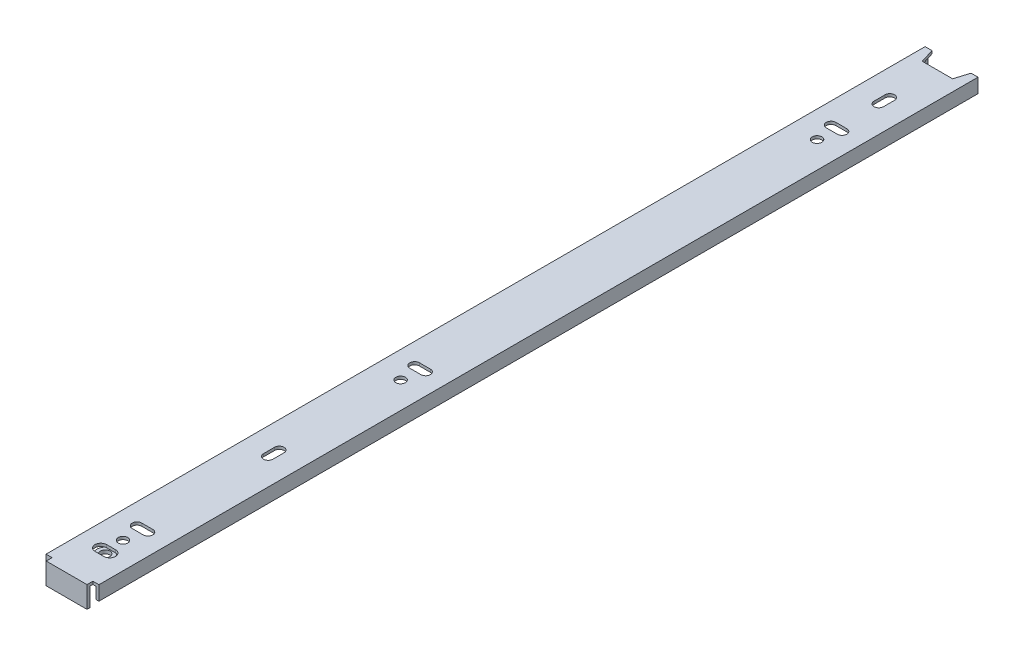
SolidWorks part; units mm, degrees
ref_plane "Front Plane" through (0, 0, 0) normal (0, 0, 1) x (1, 0, 0)
ref_plane "Top Plane" through (0, 0, 0) normal (0, 1, 0) x (1, 0, 0)
ref_plane "Right Plane" through (0, 0, 0) normal (1, 0, 0) x (0, 0, -1)
ref_plane "Plane1" through (0, -0.6, 0) normal (0, -1, 0) x (1, 0, 0)
sketch "Sketch1" plane through (0, -0.6, 0) normal (0, -1, 0) x (1, 0, 0)
  line L0 (3.75, 390.2) -> (3.1403, 397.9471)
  line L1 (-3.1403, 397.9471) -> (-3.75, 390.2)
  arc A0 (3.1403, 397.9471) -> (-3.1403, 397.9471) centre (0, 397.7) ccw
  arc A1 (-3.75, 390.2) -> (3.75, 390.2) centre (0, 390.2) ccw
extrude "Boss-Extrude1" add sketch "Sketch1" against normal blind 2.6
ref_plane "Plane2" through (0, 2, 0) normal (0, -1, 0) x (1, 0, 0)
sketch "Sketch2" plane through (0, 2, 0) normal (0, -1, 0) x (1, 0, 0)
  line L0 (-12.2, 408) -> (-12.2, 0)
  line L1 (-12.2, 0) -> (12.2, 0)
  line L2 (12.2, 0) -> (12.2, 408)
  line L3 (12.2, 408) -> (-12.2, 408)
  line L4 (-2.05, 392.9) -> (2.05, 392.9)
  line L5 (2.05, 387.5) -> (-2.05, 387.5)
  arc A0 (-2.05, 387.5) -> (-2.05, 392.9) centre (-2.05, 390.2) cw
  arc A1 (2.05, 392.9) -> (2.05, 387.5) centre (2.05, 390.2) cw
extrude "Boss-Extrude2" add sketch "Sketch2" against normal blind 1.3
sketch "Sketch3" plane through (0, 3.3, 0) normal (0, 1, 0) x (-1, 0, 0)
  line L0 (-12.2, 405.3) -> (-9.4, 405.3)
  line L1 (-9.4, 405.3) -> (-9.4, 408)
  line L2 (-9.4, 408) -> (-12.2, 408)
  line L3 (-12.2, 408) -> (-12.2, 405.3)
extrude "Cut-Extrude1" cut sketch "Sketch3" against normal through all
sketch "Sketch4" plane through (0, 2, 0) normal (0, -1, 0) x (1, 0, 0)
  line L0 (12.2, 0) -> (10.9, 0)
  line L1 (10.9, 0) -> (10.9, 405.3)
  line L2 (10.9, 405.3) -> (12.2, 405.3)
  line L3 (12.2, 405.3) -> (12.2, 0)
extrude "Boss-Extrude3" add sketch "Sketch4" along normal blind 5.3
sketch "Sketch5" plane through (0, 3.3, 0) normal (0, 1, 0) x (-1, 0, 0)
  line L0 (9.4, 405.3) -> (12.2, 405.3)
  line L1 (12.2, 405.3) -> (12.2, 408)
  line L2 (12.2, 408) -> (9.4, 408)
  line L3 (9.4, 408) -> (9.4, 405.3)
extrude "Cut-Extrude2" cut sketch "Sketch5" against normal through all
sketch "Sketch6" plane through (0, 2, 0) normal (0, -1, 0) x (1, 0, 0)
  line L0 (-10.9, 0) -> (-12.2, 0)
  line L1 (-12.2, 0) -> (-12.2, 405.3)
  line L2 (-12.2, 405.3) -> (-10.9, 405.3)
  line L3 (-10.9, 405.3) -> (-10.9, 0)
extrude "Boss-Extrude4" add sketch "Sketch6" along normal blind 5.3
sketch "Sketch7" plane through (0, 2, 0) normal (0, -1, 0) x (1, 0, 0)
  line L0 (-9.4, 406.6) -> (-9.4, 408)
  line L1 (-9.4, 408) -> (9.4, 408)
  line L2 (9.4, 408) -> (9.4, 406.6)
  line L3 (9.4, 406.6) -> (-9.4, 406.6)
extrude "Boss-Extrude5" add sketch "Sketch7" along normal blind 8.6
sketch "Sketch8" plane through (0, 3.3, 0) normal (0, 1, 0) x (-1, 0, 0)
  line L0 (-7, 0) -> (7, 0)
  line L1 (7, 0) -> (7, 6.5)
  line L2 (7, 6.5) -> (-7, 6.5)
  line L3 (-7, 6.5) -> (-7, 0)
extrude "Cut-Extrude3" cut sketch "Sketch8" against normal through all
sketch "Sketch9" plane through (0, 2, 0) normal (0, -1, 0) x (1, 0, 0)
  line L0 (2.55, 375.2) -> (-2.55, 375.2)
  line L1 (-2.55, 370.8) -> (2.55, 370.8)
  arc A0 (-2.55, 375.2) -> (-2.55, 370.8) centre (-2.55, 373) ccw
  arc A1 (2.55, 370.8) -> (2.55, 375.2) centre (2.55, 373) ccw
extrude "Cut-Extrude4" cut sketch "Sketch9" against normal through all
sketch "Sketch10" plane through (0, 2, 0) normal (0, -1, 0) x (1, 0, 0)
  line L0 (-2.5499, 242.8) -> (2.5501, 242.8)
  line L1 (2.5501, 247.2) -> (-2.5499, 247.2)
  arc A0 (2.5501, 242.8) -> (2.5501, 247.2) centre (2.5501, 245) ccw
  arc A1 (-2.5499, 247.2) -> (-2.5499, 242.8) centre (-2.5499, 245) ccw
extrude "Cut-Extrude5" cut sketch "Sketch10" against normal through all
sketch "Sketch11" plane through (0, 2, 0) normal (0, -1, 0) x (1, 0, 0)
  line L0 (2.2001, 309.95) -> (2.2001, 315.05)
  line L1 (-2.1999, 315.05) -> (-2.1999, 309.95)
  arc A0 (-2.1999, 309.95) -> (2.2001, 309.95) centre (0.0001, 309.95) ccw
  arc A1 (2.2001, 315.05) -> (-2.1999, 315.05) centre (0.0001, 315.05) ccw
extrude "Cut-Extrude6" cut sketch "Sketch11" against normal through all
sketch "Sketch12" plane through (0, 2, 0) normal (0, -1, 0) x (1, 0, 0)
  line L0 (2.2001, 28.45) -> (2.2001, 33.55)
  line L1 (-2.1999, 33.55) -> (-2.1999, 28.45)
  arc A0 (-2.1999, 28.45) -> (2.2001, 28.45) centre (0.0001, 28.45) ccw
  arc A1 (2.2001, 33.55) -> (-2.1999, 33.55) centre (0.0001, 33.55) ccw
extrude "Cut-Extrude7" cut sketch "Sketch12" against normal through all
sketch "Sketch13" plane through (0, 3.3, 0) normal (0, 1, 0) x (-1, 0, 0)
  line L0 (2.5499, 55.2) -> (-2.5501, 55.2)
  line L1 (-2.5501, 50.8) -> (2.5499, 50.8)
  arc A0 (-2.5501, 55.2) -> (-2.5501, 50.8) centre (-2.5501, 53) ccw
  arc A1 (2.5499, 50.8) -> (2.5499, 55.2) centre (2.5499, 53) ccw
extrude "Cut-Extrude8" cut sketch "Sketch13" against normal through all
sketch "Sketch14" plane through (0, -0.6, 0) normal (0, -1, 0) x (1, 0, 0)
  line L0 (0.6, 397.1) -> (2.2, 397.1)
  line L1 (2.2, 397.1) -> (2.2, 398.3)
  line L2 (2.2, 398.3) -> (0.6, 398.3)
  line L3 (0.6, 398.3) -> (0.6, 399.9)
  line L4 (0.6, 399.9) -> (-0.6, 399.9)
  line L5 (-0.6, 399.9) -> (-0.6, 398.3)
  line L6 (-0.6, 398.3) -> (-2.2, 398.3)
  line L7 (-2.2, 398.3) -> (-2.2, 397.1)
  line L8 (-2.2, 397.1) -> (-0.6, 397.1)
  line L9 (-0.6, 397.1) -> (-0.6, 395.5)
  line L10 (-0.6, 395.5) -> (0.6, 395.5)
  line L11 (0.6, 395.5) -> (0.6, 397.1)
extrude "Cut-Extrude9" cut sketch "Sketch14" against normal blind 2.6
draft "Draft1" type of draft neutral plane draft angle 17.103 faces to draft 2 face at (-7, 2.65, 3.25) face at (7, 2.65, 3.25) neutral plane through (-7, -6.6, 6.5) neutral plane normal (0, 0, -1) parameters "D1"=17.103
hole_wizard "Ø4.4 (4.4) Diameter Hole1" positions "Sketch16" profile "Sketch15" hole size "Ø4.4" standard "ANSI Metric"
sketch "Sketch16" plane through (0, 2, 0) normal (0, -1, 0) x (-1, 0, 0)
  point P0 (-0.0001, -62)
  point P1 (-0.0001, -254)
  point P2 (0, -382)
sketch "Sketch15" plane through (0.0001, 2, 62) normal (1, 0, 0) x (0, 0, -1)
  line L0 (0, 0) -> (0, 1.3)
  line L1 (0, 1.3) -> (2.2, 1.3)
  line L2 (2.2, 1.3) -> (2.2, 0)
  line L5 (2.2, 0) -> (0, 0)
  line L11 (0, -6.35) -> (0, 107.95) construction
  dimension "Thru Hole Dia." = 4.4
  dimension "Thru Hole Depth" = 1.3
hole_wizard "CBORE for M4 Hex Head Machine Screw1" positions "Sketch18" profile "Sketch17" counterbore size "M4" standard "ANSI Metric"
sketch "Sketch18" plane through (0, -0.6, 0) normal (0, -1, 0) x (-1, 0, 0)
  point P0 (0, -390.2)
sketch "Sketch17" plane through (0, -0.6, 390.2) normal (1, 0, 0) x (0, 0, -1)
  line L0 (0, 0) -> (0, 3.9)
  line L1 (0, 3.9) -> (2.2, 3.9)
  line L3 (2.2, 3.9) -> (2.2, 1)
  line L4 (2.2, 1) -> (3.75, 1)
  line L5 (3.75, 1) -> (3.75, 0)
  line L7 (3.75, 0) -> (0, 0)
  line L11 (0, -6.35) -> (0, 107.95) construction
  dimension "Thru Hole Dia." = 4.4
  dimension "Thru Hole Depth" = 3.9
  dimension "C'Bore Dia." = 7.5
  dimension "C'Bore Depth" = 1
